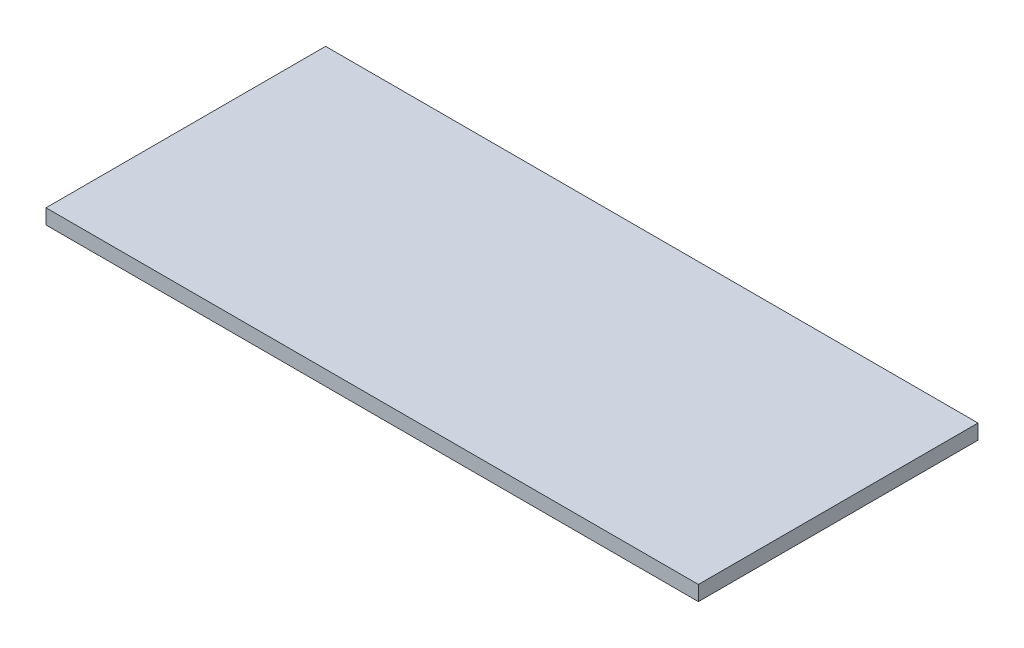
SolidWorks part; units mm, degrees
ref_plane "Front Plane" through (0, 0, 0) normal (0, 0, 1) x (1, 0, 0)
ref_plane "Top Plane" through (0, 0, 0) normal (0, 1, 0) x (1, 0, 0)
ref_plane "Right Plane" through (0, 0, 0) normal (1, 0, 0) x (0, 0, -1)
sketch "Sketch1" plane through (0, 0, 0) normal (0, 1, 0) x (1, 0, 0)
  line L1 (-35, -15) -> (35, -15)
  line L2 (-35, -15) -> (-35, 15)
  line L3 (-35, 15) -> (35, 15)
  line L4 (35, -15) -> (35, 15)
  line L5 (-35, -15) -> (35, 15) construction
  line L6 (-35, 15) -> (35, -15) construction
  point P0 (0, 0)
  dimension "D1" = 70
  dimension "D2" = 30
extrude "Boss-Extrude1" add sketch "Sketch1" along normal blind 1.6
